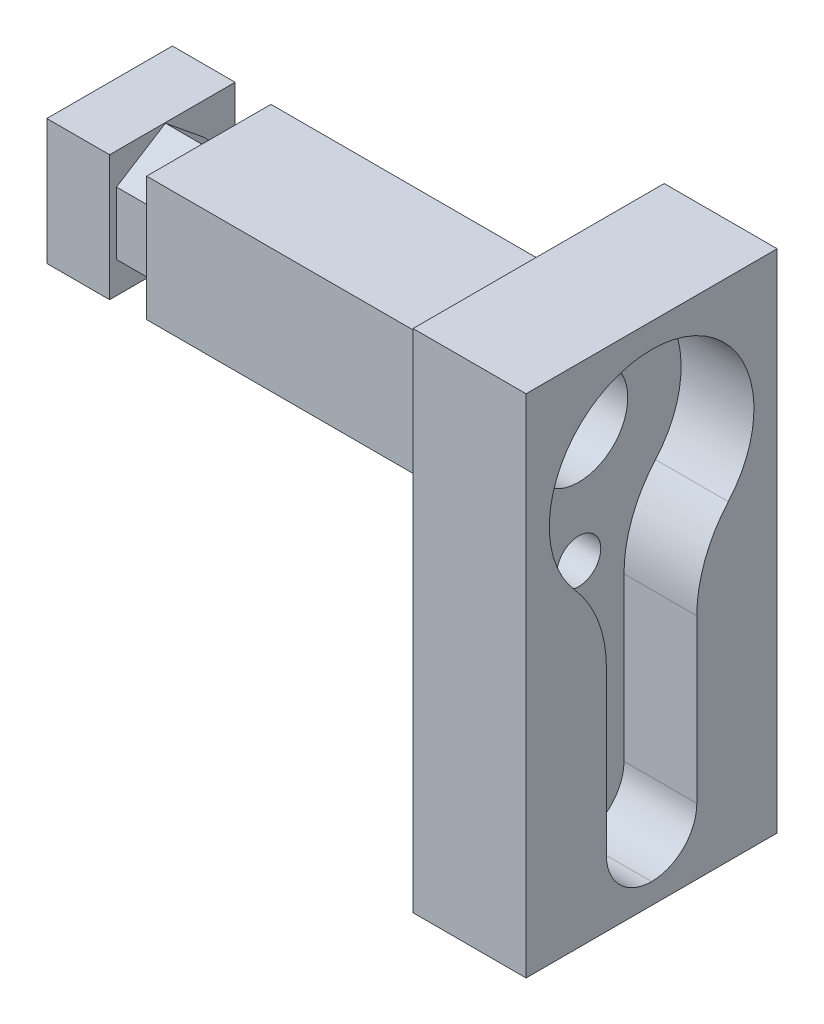
SolidWorks part; units mm, degrees
ref_plane "Front Plane" through (0, 0, 0) normal (0, 0, 1) x (1, 0, 0)
ref_plane "Top Plane" through (0, 0, 0) normal (0, 1, 0) x (1, 0, 0)
ref_plane "Right Plane" through (0, 0, 0) normal (1, 0, 0) x (0, 0, -1)
sketch "Sketch1" plane through (0, 0, 0) normal (1, 0, 0) x (0, 0, -1)
  line L1 (-10, 10) -> (10, 10)
  line L2 (-10, 10) -> (-10, -10)
  line L3 (-10, -10) -> (10, -10)
  line L4 (10, 10) -> (10, -10)
  line L5 (-10, 10) -> (10, -10) construction
  line L6 (-10, -10) -> (10, 10) construction
  point P0 (0, 0)
  dimension "D1" = 20
  dimension "D2" = 20
extrude "Boss-Extrude1" add sketch "Sketch1" along normal blind 20
sketch "Sketch2" plane through (20, 0, 0) normal (1, 0, 0) x (0, 0, -1)
  line L1 (-22.5, 35) -> (22.5, 35)
  line L2 (-22.5, 35) -> (-22.5, -35)
  line L3 (-22.5, -35) -> (22.5, -35)
  line L4 (22.5, 35) -> (22.5, -35)
  line L5 (-22.5, 35) -> (22.5, -35) construction
  line L6 (-22.5, -35) -> (22.5, 35) construction
  point P0 (0, 0)
  dimension "D1" = 45
  dimension "D2" = 70
extrude "Boss-Extrude2" add sketch "Sketch2" along normal blind 12
sketch "Sketch4" plane through (32, 0, 0) normal (1, 0, 0) x (0, 0, -1)
  line L0 (0, 7.65) -> (0, 8.1702) construction
  line L1 (7.65, 7.65) -> (-7.65, 7.65) construction
  line L17 (3.6, -26.55) -> (-3.6, -26.55) construction
  line L18 (-7.65, 7.65) -> (7.65, 7.65) construction
  line L22 (-7.65, 7.65) -> (-7.65, -27.55) construction
  line L23 (-7.65, -27.55) -> (7.65, -27.55) construction
  line L24 (7.65, 7.65) -> (7.65, -27.55) construction
  line L25 (-7.65, 7.65) -> (7.65, -27.55) construction
  line L26 (-7.65, -27.55) -> (7.65, 7.65) construction
  line L27 (3.6, -26.55) -> (3.6, -28.55) construction
  line L28 (3.6, -28.55) -> (-3.6, -28.55) construction
  line L29 (-3.6, -26.55) -> (-3.6, -28.55) construction
  line L30 (3.6, -26.55) -> (-3.6, -28.55) construction
  line L31 (3.6, -28.55) -> (-3.6, -26.55) construction
  line L34 (3.6, -28.55) -> (-3.6, -28.55)
  line L35 (-3.6, -28.55) -> (-3.6, -7.3118)
  line L36 (3.6, -28.55) -> (3.6, -7.3118)
  arc A1 (3.6, -6.75) -> (-3.6, -6.75) centre (0, 0) ccw construction
  arc A2 (3.6, -7.3118) -> (-3.6, -7.3118) centre (0, 0) ccw
  point P1 (0, -27.55)
  point P7 (0, -13.75)
  point P10 (0, 7.65)
  point P14 (0, -9.95)
  dimension "D1" = 15.3
  dimension "D5" = 2
  dimension "D2" = 15.3
  dimension "D3" = 35.2
  dimension "D4" = 7.2
extrude "Cut-Extrude1" cut sketch "Sketch4" against normal blind 5.8
fillet "Fillet1" radius 3.6 2 edges at (29.1, -28.55, 3.6) (29.1, -28.55, -3.6)
fillet "Fillet2" radius 10 2 edges at (29.1, -7.3118, 3.6) (29.1, -7.3118, -3.6)
sketch "Sketch5" plane through (0, 0, 0) normal (-1, 0, 0) x (0, 0, 1)
  circle A0 centre (0, 0) radius 3.9
  dimension "D1" = 7.8
extrude "Cut-Extrude2" cut sketch "Sketch5" against normal through all
sketch "Sketch6" plane through (26.2, 0, 0) normal (1, 0, 0) x (0, 0, -1)
  line L0 (0, -19.35) -> (0, 0) construction
  line L1 (0, -25.65) -> (0, -23.15) construction
  line L2 (0, -23.15) -> (0, -21.85) construction
  line L3 (0, -21.85) -> (0, -19.35) construction
  line L5 (0, 0) -> (1.164, 0) construction
  line L6 (0, 0) -> (0, -9.35) construction
  line L7 (0, -9.35) -> (1.164, -9.35) construction
  line L8 (1.164, 0) -> (1.164, -9.35) construction
  line L9 (0, 0) -> (1.164, -9.35) construction
  line L10 (0, -9.35) -> (1.164, 0) construction
  circle A0 centre (0, -20.6) radius 1.75
  circle A1 centre (0, -9.35) radius 1.75
  point P11 (0.582, -4.675)
  dimension "D5" = 3.5
  dimension "D6" = 9.35
  dimension "D7" = 3.5
  dimension "D1" = 19.35
  dimension "D2" = 2.5
  dimension "D3" = 1.3
  dimension "D4" = 2.5
extrude "Cut-Extrude3" cut sketch "Sketch6" against normal up to next
sketch "Sketch7" plane through (0, -35, 0) normal (0, -1, 0) x (1, 0, 0)
  line L1 (32, 22.5) -> (20, 22.5)
  line L2 (32, 22.5) -> (32, -22.5)
  line L3 (32, -22.5) -> (20, -22.5)
  line L4 (20, 22.5) -> (20, -22.5)
  line L5 (32, 22.5) -> (20, -22.5) construction
  line L6 (32, -22.5) -> (20, 22.5) construction
  point P5 (26, 0)
extrude "Cut-Extrude4" cut sketch "Sketch7" against normal blind 4.8
sketch "Sketch9" plane through (0, 35, 0) normal (0, 1, 0) x (1, 0, 0)
  line L1 (32, 22.5) -> (20, 22.5)
  line L2 (32, 22.5) -> (32, -22.5)
  line L3 (32, -22.5) -> (20, -22.5)
  line L4 (20, 22.5) -> (20, -22.5)
  line L5 (32, 22.5) -> (20, -22.5) construction
  line L6 (32, -22.5) -> (20, 22.5) construction
  point P4 (26, 0)
extrude "Cut-Extrude5" cut sketch "Sketch9" against normal blind 23.8
sketch "Sketch10" plane through (20, 0, 0) normal (-1, 0, 0) x (0, 0, 1)
  line L0 (-22.5, 11.2) -> (22.5, 11.2) construction
  line L1 (-10, 11.2) -> (-22.5, 11.2)
  line L2 (-10, 11.2) -> (-10, -30.2)
  line L3 (-10, -30.2) -> (-22.5, -30.2)
  line L4 (-22.5, 11.2) -> (-22.5, -30.2)
  line L5 (-10, 11.2) -> (-22.5, -30.2) construction
  line L6 (-10, -30.2) -> (-22.5, 11.2) construction
  line L7 (22.5, -30.2) -> (-22.5, -30.2) construction
  line L9 (10, 11.2) -> (22.5, 11.2)
  line L10 (10, 11.2) -> (10, -30.2)
  line L11 (10, -30.2) -> (22.5, -30.2)
  line L12 (22.5, 11.2) -> (22.5, -30.2)
  line L13 (10, 11.2) -> (22.5, -30.2) construction
  line L14 (10, -30.2) -> (22.5, 11.2) construction
  point P4 (-16.25, -9.5)
  point P13 (16.25, -9.5)
extrude "Cut-Extrude6" cut sketch "Sketch10" against normal blind 23.8
sketch "Sketch11" plane through (20, 0, 0) normal (-1, 0, 0) x (0, 0, 1)
  line L5 (-10, 11.2) -> (10, 11.2)
  line L6 (-10, 11.2) -> (-10, 10)
  line L7 (-10, 10) -> (10, 10)
  line L8 (10, 11.2) -> (10, 10)
  line L9 (-10, 11.2) -> (10, 10) construction
  line L10 (-10, 10) -> (10, 11.2) construction
  point P4 (0, 10.6)
extrude "Cut-Extrude7" cut sketch "Sketch11" against normal blind 23.8
sketch "Sketch12" plane through (0, 0, 0) normal (-1, 0, 0) x (0, 0, 1)
  line L1 (10, 10) -> (-10, 10)
  line L2 (10, 10) -> (10, -10)
  line L3 (10, -10) -> (-10, -10)
  line L4 (-10, 10) -> (-10, -10)
  line L5 (10, 10) -> (-10, -10) construction
  line L6 (10, -10) -> (-10, 10) construction
  circle A0 centre (0, 0) radius 3.9
  point P4 (0, 0)
extrude "Boss-Extrude3" add sketch "Sketch12" along normal blind 20
sketch "Sketch13" plane through (-20, 0, 0) normal (-1, 0, 0) x (0, 0, 1)
  line L8 (10.1, -10.1) -> (10.1, 10.1)
  line L9 (10.1, 10.1) -> (-10.1, 10.1)
  line L10 (-10.1, 10.1) -> (-10.1, -10.1)
  line L11 (-10.1, -10.1) -> (10.1, -10.1)
  line L12 (10.1, -10.1) -> (10.1, 10.1)
  line L13 (10.1, 10.1) -> (-10.1, 10.1)
  line L14 (-10.1, 10.1) -> (-10.1, -10.1)
  line L15 (-10.1, -10.1) -> (10.1, -10.1)
  circle A0 centre (0, 0) radius 3.9
  dimension "D1" = 0.1
extrude "Boss-Extrude4" add sketch "Sketch13" against normal up to surface (40 mm away) up to face at (20, -20.6, -1.75)
sketch "Sketch14" plane through (0, 10, 0) normal (0, 1, 0) x (1, 0, 0)
  line L1 (32, 10) -> (20, 10)
  line L2 (32, 10) -> (32, -10)
  line L3 (32, -10) -> (20, -10)
  line L4 (20, 10) -> (20, -10)
  line L5 (32, 10) -> (20, -10) construction
  line L6 (32, -10) -> (20, 10) construction
  point P4 (26, 0)
extrude "Boss-Extrude5" add sketch "Sketch14" along normal blind 0.1
sketch "Sketch17" plane through (-20, 0, 0) normal (-1, 0, 0) x (0, 0, 1)
  circle A0 centre (0, 0) radius 4.8309
extrude "Boss-Extrude8" add sketch "Sketch17" against normal blind 39
sketch "Sketch18" plane through (-20, 0, 0) normal (-1, 0, 0) x (0, 0, 1)
  line L5 (10.1, 10.1) -> (-15.5388, 10.1)
  line L6 (10.1, 10.1) -> (10.1, -36.522)
  line L7 (10.1, -36.522) -> (-15.5388, -36.522)
  line L8 (-15.5388, 10.1) -> (-15.5388, -36.522)
  line L9 (10.1, 10.1) -> (-15.5388, -36.522) construction
  line L10 (10.1, -36.522) -> (-15.5388, 10.1) construction
  point P4 (-2.7194, -13.211)
extrude "Cut-Extrude8" cut sketch "Sketch18" against normal blind 43
sketch "Sketch19" plane through (23, 0, 0) normal (-1, 0, 0) x (0, 0, 1)
  line L1 (4.95, 4.95) -> (-4.95, 4.95)
  line L2 (4.95, 4.95) -> (4.95, -4.95)
  line L3 (4.95, -4.95) -> (-4.95, -4.95)
  line L4 (-4.95, 4.95) -> (-4.95, -4.95)
  line L5 (4.95, 4.95) -> (-4.95, -4.95) construction
  line L6 (4.95, -4.95) -> (-4.95, 4.95) construction
  point P0 (0, 0)
  dimension "D1" = 9.9
  dimension "D2" = 9.9
extrude "Boss-Extrude9" add sketch "Sketch19" along normal blind 26.27
sketch "Sketch20" plane through (-3.27, 0, 0) normal (-1, 0, 0) x (0, 0, 1)
  line L0 (-4.95, 0) -> (-4.95, 2.5) construction
  line L1 (-4.95, 4.95) -> (-4.95, -4.95) construction
  line L2 (-4.95, 0) -> (-4.95, -2.5) construction
  line L3 (-4.95, 2.5) -> (4.95, 2.5) construction
  line L4 (4.95, -4.95) -> (4.95, 4.95) construction
  line L5 (-4.95, -2.5) -> (4.95, -2.5) construction
  line L6 (-4.95, 4.95) -> (0.55, 4.95) construction
  line L7 (4.95, 4.95) -> (-4.95, 4.95) construction
  line L8 (-4.95, -4.95) -> (0.55, -4.95) construction
  line L9 (-4.95, -4.95) -> (4.95, -4.95) construction
  line L10 (0.55, 4.95) -> (-2.45, 2.5)
  line L11 (-4.95, 2.5) -> (-2.45, 2.5) construction
  line L12 (0.55, 4.95) -> (4.45, 2.5)
  line L13 (4.95, 2.5) -> (4.45, 2.5) construction
  line L14 (4.95, 2.5) -> (4.95, -2.5) construction
  line L15 (4.95, -2.5) -> (4.45, -2.5) construction
  line L16 (4.45, 2.5) -> (4.45, -2.5) construction
  line L17 (4.95, 2.5) -> (4.45, -2.5) construction
  line L18 (4.95, -2.5) -> (4.45, 2.5) construction
  line L19 (4.45, 2.5) -> (4.45, -2.5)
  line L20 (4.45, -2.5) -> (0.55, -4.95)
  line L21 (-4.95, 2.5) -> (-4.95, -2.5) construction
  line L22 (-4.95, -2.5) -> (-2.45, -2.5) construction
  line L23 (-2.45, 2.5) -> (-2.45, -2.5) construction
  line L24 (-4.95, 2.5) -> (-2.45, -2.5) construction
  line L25 (-4.95, -2.5) -> (-2.45, 2.5) construction
  line L26 (-2.45, 2.5) -> (-2.45, -2.5)
  line L27 (-2.45, -2.5) -> (0.55, -4.95)
  point P21 (4.7, 0)
  point P24 (-3.7, 0)
  dimension "D1" = 2.5
  dimension "D2" = 2.5
  dimension "D3" = 5.5
  dimension "D4" = 5.5
  dimension "D5" = 0.5
  dimension "D6" = 2.5
extrude "Boss-Extrude10" add sketch "Sketch20" along normal blind 2.9
sketch "Sketch21" plane through (-6.17, 0, 0) normal (-1, 0, 0) x (0, 0, 1)
  line L1 (5, 5) -> (-5, 5)
  line L2 (5, 5) -> (5, -5)
  line L3 (5, -5) -> (-5, -5)
  line L4 (-5, 5) -> (-5, -5)
  line L5 (5, 5) -> (-5, -5) construction
  line L6 (5, -5) -> (-5, 5) construction
  point P0 (0, 0)
  dimension "D1" = 10
  dimension "D2" = 10
extrude "Boss-Extrude11" add sketch "Sketch21" along normal blind 5
